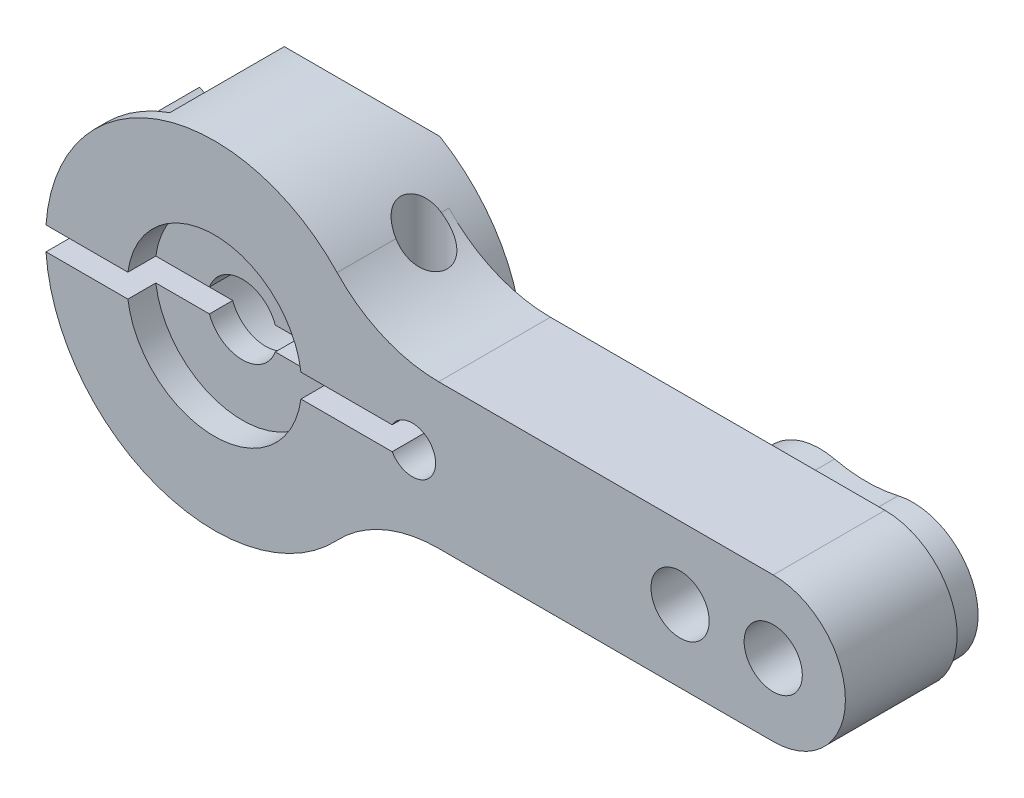
SolidWorks part; units mm, degrees
ref_plane "Спереди (XY)" through (0, 0, 0) normal (0, 0, 1) x (1, 0, 0)
ref_plane "Сверху (XZ)" through (0, 0, 0) normal (0, 1, 0) x (1, 0, 0)
ref_plane "Справа (ZY)" through (0, 0, 0) normal (1, 0, 0) x (0, 0, -1)
sketch "Эскиз1" plane through (0, 0, 0) normal (0, 0, 1) x (1, 0, 0)
  line L0 (24, 3.1) -> (6.5538, 3.1)
  line L1 (24, -3.1) -> (6.5538, -3.1)
  line L2 (24, 0) -> (20, 0) construction
  line L3 (1.4142, 0.5) -> (7.634, 0.5)
  line L4 (0, 0) -> (12.6344, 0) construction
  line L5 (1.4142, -0.5) -> (7.634, -0.5)
  line L6 (-1.4142, 0.5) -> (-7.2327, 0.5)
  line L7 (-1.4142, -0.5) -> (-7.2327, -0.5)
  circle A0 centre (0, 0) radius 1.5
  circle A1 centre (0, 0) radius 2.75
  circle A2 centre (0, 0) radius 7.25
  arc A3 (24, -3.1) -> (24, 3.1) centre (24, 0) ccw
  circle A4 centre (24, 0) radius 1.25
  arc A5 (23.3636, -2.7267) -> (23.3636, 2.7267) centre (24, 0) ccw
  circle A6 centre (20, 0) radius 1.25
  arc A7 (20.6364, 2.7267) -> (20.6364, -2.7267) centre (20, 0) ccw
  circle A8 centre (0, 0) radius 3.75
  arc A9 (20.6364, -2.7267) -> (23.3636, -2.7267) centre (22, -8.5697) cw
  arc A10 (20.6364, 2.7267) -> (23.3636, 2.7267) centre (22, 8.5697) ccw
  circle A11 centre (8.5, 0) radius 1
  point P31 (0, 0)
  dimension "D1" = 14.5
  dimension "D2" = 3
  dimension "D3" = 5.5
  dimension "D4" = 7.5
  dimension "D6" = 20
  dimension "D7" = 24
  dimension "D8" = 2.5
  dimension "D9" = 5.6
  dimension "D10" = 6
  dimension "D12" = 2
  dimension "D13" = 8.5
  dimension "D5" = 6.2
  dimension "D11" = 1
extrude "Бобышка-Вытянуть1" add sketch "Эскиз1" along normal blind 6 contours A11 L5 A2 L1 A3 L0 L3 A7 A10 A5 A9 | A10 A7 A9 A5 A6 A4 | A8 L3 A2 L6 | L3 A8 L6 A1 | L3 A1 L6 A0 | A8 L7 A2 L5 | L7 A8 L5 A1 | L7 A1 L5 A0 region at (13.7327, 0, 0) region at (0, 3.8269, 0) region at (0, -3.8269, 0) region at (0, 3.6689, 0) region at (0, 1.5952, 0) region at (-3.2103, -0.5811, 0) region at (0, -1.5952, 0) region at (22, 0, 0)
extrude "Вырез-Вытянуть1" cut sketch "Эскиз1<3>" along normal blind 1.2 contours A11 L5 A2 L1 A3 L0 L3 A7 A10 A5 A9 region at (13.7327, 0, 0)
sketch "Эскиз1<3>" plane through (0, 0, 0) normal (0, 0, 1) x (1, 0, 0) same geometry as "Эскиз1"
extrude "Вырез-Вытянуть2" cut sketch "Эскиз1<4>" along normal blind 3.8 contours A1
sketch "Эскиз1<4>" plane through (0, 0, 0) normal (0, 0, 1) x (1, 0, 0) same geometry as "Эскиз1"
extrude "Вырез-Вытянуть3" cut sketch "Эскиз1<5>" against normal blind 1.2 from surface contours A8 starting at face at (5.4057, 0, 6)
sketch "Эскиз1<5>" plane through (0, 0, 0) normal (0, 0, 1) x (1, 0, 0) same geometry as "Эскиз1"
fillet "Скругление1" radius 6 2 edges at (6.5538, -3.1, 3.6) (6.5538, 3.1, 3.6)
sketch "Эскиз2" plane through (0, 0, 0) normal (0, 0, 1) x (1, 0, 0)
  line L0 (0, 0) -> (-5.099, 5.5) construction
  line L1 (0, 0) -> (10.198, -11) construction
  line L2 (-2.7042, 0.5) -> (-7.2327, 0.5) construction
  circle A0 centre (5.099, -5.5) radius 3
  circle A1 centre (-5.099, 5.5) radius 3
  circle A2 centre (0, 0) radius 7.5 construction
  point P7 (-5.099, 2.5)
  point P11 (0, 0)
  dimension "D1" = 6
  dimension "D3" = 15
  dimension "D2" = 2
extrude "Вырез-Вытянуть4" cut sketch "Эскиз2" along normal blind 5.5
sketch "Эскиз3" plane through (0, 0, 0) normal (0, 1, 0) x (1, 0, 0)
  line L0 (0, 0) -> (0, -19.0596) construction
  line L1 (-7.2327, -6) -> (5.2697, -6) construction
  circle A0 centre (5.5, -2.5) radius 1
  circle A1 centre (-5.5, -2.5) radius 1
  dimension "D3" = 2
  dimension "D1" = 3.5
  dimension "D2" = 5.5
extrude "Вырез-Вытянуть5" cut sketch "Эскиз3" against normal through all both and the other way through all
sketch "Эскиз4" plane through (0, 0, 0) normal (1, 0, 0) x (0, 0, -1)
  line L0 (0, -6.25) -> (-1, -7.25)
  line L1 (-1, -7.25) -> (0, -7.25)
  line L2 (0, -7.25) -> (0, -6.25)
  line L3 (0, -7.25) -> (0, -0.5) construction
  line L4 (-6, -7.25) -> (0, -7.25) construction
  line L5 (0, 0) -> (12.563, 0) construction
  line L6 (0, 7.25) -> (0, 6.25)
  line L7 (-1, 7.25) -> (0, 7.25)
  line L8 (0, 6.25) -> (-1, 7.25)
  dimension "D1" = 1
extrude "Вырез-Вытянуть6" cut sketch "Эскиз4" against normal through all both and the other way through all
